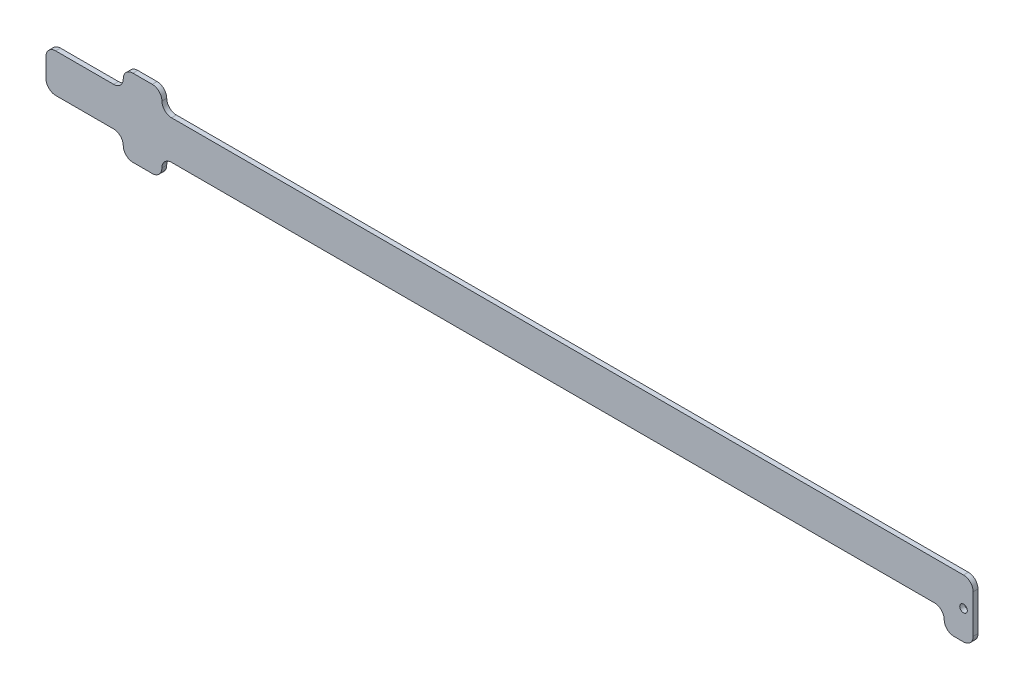
SolidWorks part; units mm, degrees
material "PC High Viscosity"
ref_plane "Front Plane" through (0, 0, 0) normal (0, 0, 1) x (1, 0, 0)
ref_plane "Top Plane" through (0, 0, 0) normal (0, 1, 0) x (1, 0, 0)
ref_plane "Right Plane" through (0, 0, 0) normal (1, 0, 0) x (0, 0, -1)
sketch "Sketch1" plane through (0, 0, 0) normal (0, 0, 1) x (1, 0, 0)
  line L0 (50.8, 0) -> (50.8, -12.7)
  line L1 (0, 0) -> (590.55, 0)
  line L2 (0, 0) -> (0, 25.4)
  line L3 (0, 25.4) -> (609.6, 25.4)
  line L4 (609.6, 0) -> (609.6, 25.4)
  line L5 (50.8, 38.1) -> (76.2, 38.1)
  line L6 (76.2, 38.1) -> (76.2, 25.4)
  line L7 (50.8, 38.1) -> (50.8, 25.4)
  line L8 (76.2, 0) -> (76.2, -12.7)
  line L9 (76.2, -12.7) -> (50.8, -12.7)
  line L10 (590.55, 0) -> (590.55, -12.7)
  line L11 (609.6, 10.0162) -> (603.25, 13.6823) construction
  line L12 (603.25, 13.6823) -> (596.9, 10.0162) construction
  line L13 (596.9, 10.0162) -> (596.9, 2.6838) construction
  line L14 (596.9, 2.6838) -> (603.25, -0.9823) construction
  line L15 (603.25, -0.9823) -> (609.6, 2.6838) construction
  line L16 (609.6, 2.6838) -> (609.6, 10.0162) construction
  line L17 (609.6, 0) -> (609.6, -12.7)
  line L18 (609.6, -12.7) -> (590.55, -12.7)
  circle A0 centre (603.25, 6.35) radius 2.4892
  circle A1 centre (603.25, 6.35) radius 6.35 construction
  point P24 (0, 0)
  dimension "D5" = 4.9784
  dimension "D6" = 12.7
  dimension "D7" = 12.7
  dimension "D1" = 609.6
  dimension "D2" = 25.4
  dimension "D3" = 25.4
  dimension "D4" = 50.8
  dimension "D8" = 19.05
  dimension "D9" = 12.7
extrude "Boss-Extrude1" add sketch "Sketch1" along normal blind 3.175 contours L6 L5 L3 | L1 L4 L3 L2 A0 | L9 L8 L1 region at (63.5, -6.35, 0) region at (308.9784, 12.4144, 0) region at (63.5, 31.75, 0)
fillet "Fillet2" radius 6.35 14 edges at (76.2, 38.1, 1.5875) (76.2, 25.4, 1.5875) (609.6, 25.4, 1.5875) (76.2, 0, 1.5875) (76.2, -12.7, 1.5875) (50.8, -12.7, 1.5875) (50.8, 0, 1.5875) (0, 0, 1.5875) (50.8, 38.1, 1.5875) (50.8, 25.4, 1.5875) (0, 25.4, 1.5875) (590.55, 0, 1.5875) (590.55, -12.7, 1.5875) (609.6, -12.7, 1.5875)
